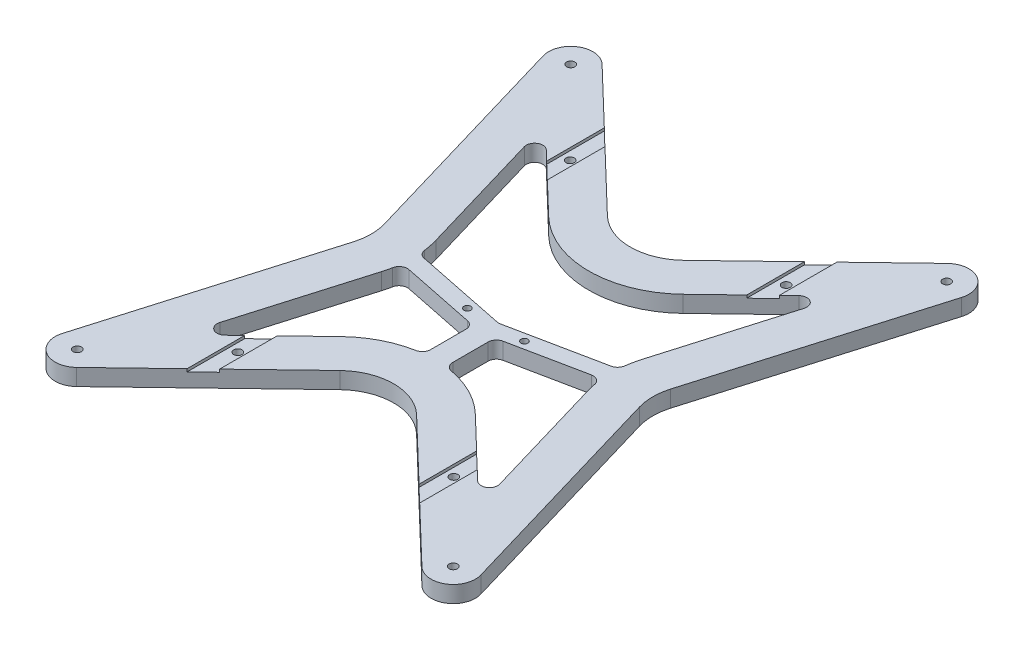
SolidWorks part; units mm, degrees
material "1060 Alloy"
ref_plane "Front Plane" through (0, 0, 0) normal (0, 0, 1) x (1, 0, 0)
ref_plane "Top Plane" through (0, 0, 0) normal (0, 1, 0) x (1, 0, 0)
ref_plane "Right Plane" through (0, 0, 0) normal (1, 0, 0) x (0, 0, -1)
sketch "Sketch1" plane through (0, 0, 0) normal (0, 1, 0) x (1, 0, 0)
  line L0 (-62.3411, 94.8657) -> (0, 35)
  line L1 (0, 35) -> (62.3411, 94.8657)
  line L2 (75.5568, 86.8368) -> (50, 0)
  line L3 (50, 0) -> (75.5568, -86.8368)
  line L4 (62.3411, -94.8657) -> (0, -35)
  line L5 (0, -35) -> (-62.3411, -94.8657)
  line L6 (-75.5568, -86.8368) -> (-50, 0)
  line L7 (-50, 0) -> (-75.5568, 86.8368)
  line L8 (-78.4889, 78.4889) -> (78.4889, -78.4889) construction
  line L9 (-42, 70) -> (-36, 70) construction
  line L10 (-42, 70) -> (-42, 50) construction
  line L11 (-42, 50) -> (-36, 50) construction
  line L12 (-36, 70) -> (-36, 50) construction
  line L13 (-42, 70) -> (-36, 50) construction
  line L14 (-42, 50) -> (-36, 70) construction
  line L15 (36, 70) -> (42, 70) construction
  line L16 (36, 70) -> (36, 50) construction
  line L17 (36, 50) -> (42, 50) construction
  line L18 (42, 70) -> (42, 50) construction
  line L19 (36, 70) -> (42, 50) construction
  line L20 (36, 50) -> (42, 70) construction
  line L21 (36, -50) -> (42, -50) construction
  line L22 (36, -50) -> (36, -70) construction
  line L23 (36, -70) -> (42, -70) construction
  line L24 (42, -50) -> (42, -70) construction
  line L25 (36, -50) -> (42, -70) construction
  line L26 (36, -70) -> (42, -50) construction
  line L27 (-42, -50) -> (-36, -50) construction
  line L28 (-42, -50) -> (-42, -70) construction
  line L29 (-42, -70) -> (-36, -70) construction
  line L30 (-36, -50) -> (-36, -70) construction
  line L31 (-42, -50) -> (-36, -70) construction
  line L32 (-42, -70) -> (-36, -50) construction
  line L33 (111, 45.9777) -> (45.9777, 111) construction
  line L34 (45.9777, 111) -> (-45.9777, 111) construction
  line L35 (-45.9777, 111) -> (-111, 45.9777) construction
  line L36 (-111, 45.9777) -> (-111, -45.9777) construction
  line L37 (-111, -45.9777) -> (-45.9777, -111) construction
  line L38 (-45.9777, -111) -> (45.9777, -111) construction
  line L39 (45.9777, -111) -> (111, -45.9777) construction
  line L40 (111, -45.9777) -> (111, 45.9777) construction
  line L41 (78.4889, 78.4889) -> (-78.4889, -78.4889) construction
  circle A0 centre (-67.8823, 89.0955) radius 1.5
  circle A1 centre (67.8823, 89.0955) radius 1.5
  circle A2 centre (-67.8823, -89.0955) radius 1.5
  circle A3 centre (67.8823, -89.0955) radius 1.5
  arc A4 (-62.3411, 94.8657) -> (-75.5568, 86.8368) centre (-67.8823, 89.0955) ccw
  arc A5 (62.3411, 94.8657) -> (75.5568, 86.8368) centre (67.8823, 89.0955) cw
  arc A6 (-75.5568, -86.8368) -> (-62.3411, -94.8657) centre (-67.8823, -89.0955) ccw
  arc A7 (75.5568, -86.8368) -> (62.3411, -94.8657) centre (67.8823, -89.0955) cw
  circle A8 centre (0, 0) radius 111 construction
  circle A9 centre (-39, 60) radius 1.5
  circle A10 centre (39, 60) radius 1.5
  circle A11 centre (39, -60) radius 1.5
  circle A12 centre (-39, -60) radius 1.5
  ellipse E0 centre (0, 0) end of major axis (50, 0) minor radius 35 construction
  dimension "D5" = 3
  dimension "D6" = 35
  dimension "D7" = 8
  dimension "D12" = 3
  dimension "D3" = 15
  dimension "D4" = 15
  dimension "D8" = 120
  dimension "D9" = 78
  dimension "D10" = 0
  dimension "D11" = 60
  dimension "D13" = 50
  dimension "D14" = 39
  dimension "D15" = 20
  dimension "D16" = 6
  dimension "D17" = 111
  dimension "D18" = 15
extrude "Boss-Extrude1" add sketch "Sketch1" along normal blind 6
fillet "Fillet1" radius 20 4 edges at (0, 3, -35) (-50, 3, 0) (0, 3, 35) (50, 3, 0)
sketch "Sketch2" plane through (0, 6, 0) normal (0, 1, 0) x (1, 0, 0)
  line L44 (-53.7292, 65.7994) -> (-37.2721, 9.8817)
  line L45 (-37.2721, -9.8817) -> (-53.7292, -65.7994)
  line L46 (-53.7292, -65.7994) -> (-24.2425, -37.4835)
  line L47 (24.2425, -37.4835) -> (53.7292, -65.7994)
  line L48 (53.7292, -65.7994) -> (37.2721, -9.8817)
  line L49 (37.2721, 9.8817) -> (53.7292, 65.7994)
  line L50 (53.7292, 65.7994) -> (24.2425, 37.4835)
  line L51 (-24.2425, 37.4835) -> (-53.7292, 65.7994)
  line L52 (-53.7292, 65.7994) -> (-37.2721, 9.8817)
  line L53 (-37.2721, -9.8817) -> (-53.7292, -65.7994)
  line L54 (-53.7292, -65.7994) -> (-24.2425, -37.4835)
  line L55 (24.2425, -37.4835) -> (53.7292, -65.7994)
  line L56 (53.7292, -65.7994) -> (37.2721, -9.8817)
  line L57 (37.2721, 9.8817) -> (53.7292, 65.7994)
  line L58 (53.7292, 65.7994) -> (24.2425, 37.4835)
  line L59 (-24.2425, 37.4835) -> (-53.7292, 65.7994)
  arc A40 (-37.2721, -9.8817) -> (-37.2721, 9.8817) centre (-70.8482, 0) ccw
  arc A41 (24.2425, -37.4835) -> (-24.2425, -37.4835) centre (0, -62.7284) ccw
  arc A42 (37.2721, 9.8817) -> (37.2721, -9.8817) centre (70.8482, 0) ccw
  arc A43 (-24.2425, 37.4835) -> (24.2425, 37.4835) centre (0, 62.7284) ccw
  arc A44 (-37.2721, -9.8817) -> (-37.2721, 9.8817) centre (-70.8482, 0) ccw
  arc A45 (24.2425, -37.4835) -> (-24.2425, -37.4835) centre (0, -62.7284) ccw
  arc A46 (37.2721, 9.8817) -> (37.2721, -9.8817) centre (70.8482, 0) ccw
  arc A47 (-24.2425, 37.4835) -> (24.2425, 37.4835) centre (0, 62.7284) ccw
  dimension "D1" = 15
extrude "Cut-Extrude1" cut sketch "Sketch2" against normal up to next
sketch "Sketch5" plane through (0, 6, 0) normal (0, 1, 0) x (1, 0, 0)
  line L0 (-38.2479, 2.9393) -> (0, -4.8715)
  line L1 (-12.94, -8.43) -> (12.94, -8.43) construction
  line L2 (-12.94, -8.43) -> (-12.94, 8.43) construction
  line L3 (-12.94, 8.43) -> (12.94, 8.43) construction
  line L4 (12.94, -8.43) -> (12.94, 8.43) construction
  line L5 (-12.94, -8.43) -> (12.94, 8.43) construction
  line L6 (-12.94, 8.43) -> (12.94, -8.43) construction
  line L8 (0, -4.8715) -> (38.2479, 2.9393)
  line L10 (38.2479, 2.9393) -> (39.4484, -2.9393)
  line L11 (39.4484, -2.9393) -> (4, -10.1785)
  line L12 (4, -10.1785) -> (4, -27.9577)
  line L13 (-4, -27.9577) -> (-4, -10.1785)
  line L14 (-4, -10.1785) -> (-39.4484, -2.9393)
  line L15 (-39.4484, -2.9393) -> (-38.2479, 2.9393)
  line L17 (38.8482, 0) -> (-38.8482, 0) construction
  circle A0 centre (-10.3, -5.83) radius 1.25
  circle A1 centre (10.3, -5.83) radius 1.25
  arc A2 (24.2425, -37.4835) -> (-24.2425, -37.4835) centre (0, -62.7284) ccw construction
  arc A3 (4, -27.9577) -> (-4, -27.9577) centre (0, -62.7284) ccw
  arc A4 (-37.2721, -9.8817) -> (-37.2721, 9.8817) centre (-70.8482, 0) ccw construction
  arc A5 (37.2721, 9.8817) -> (37.2721, -9.8817) centre (70.8482, 0) ccw construction
  circle A6 centre (38.8482, 0) radius 3 construction
  circle A7 centre (-38.8482, 0) radius 3 construction
  point P0 (0, 0)
  dimension "D3" = 2.5
  dimension "D10" = 6
  dimension "D1" = 16.86
  dimension "D2" = 25.88
  dimension "D4" = 20.6
  dimension "D5" = 2.64
  dimension "D6" = 2.6
  dimension "D7" = 6
  dimension "D8" = 3
  dimension "D9" = 8
extrude "Boss-Extrude2" add sketch "Sketch5" against normal up to surface (6 mm away) up to face at (0, 0, 0)
fillet "Fillet2" radius 3 13 edges at (53.7292, 3, 65.7994) (-53.7292, 3, 65.7994) (53.7292, 3, -65.7994) (-53.7292, 3, -65.7994) (0, 3, 4.8715) (4, 3, 10.1785) (4, 3, 27.9577) (-4, 3, 27.9577) (-4, 3, 10.1785) (35.9352, 3, -2.467) (-35.9352, 3, -2.467) (36.0376, 3, 3.6359) (-36.0376, 3, 3.6359)
sketch "Sketch6" plane through (0, 6, 0) normal (0, 1, 0) x (1, 0, 0)
  line L0 (-13.8528, 48.3028) -> (-62.3411, 94.8657) construction
  line L1 (-42, -48) -> (-36, -48)
  line L2 (-42, -48) -> (-42, -75.3323)
  line L3 (-42, -75.3323) -> (-36, -75.3323)
  line L4 (-36, -48) -> (-36, -75.3323)
  line L5 (36, -48) -> (42, -48)
  line L6 (36, -48) -> (36, -75.3323)
  line L7 (36, -75.3323) -> (42, -75.3323)
  line L8 (42, -48) -> (42, -75.3323)
  line L9 (36, 48) -> (42, 48)
  line L10 (36, 48) -> (36, 75.3323)
  line L11 (36, 75.3323) -> (42, 75.3323)
  line L12 (42, 48) -> (42, 75.3323)
  line L13 (-42, 48) -> (-36, 48)
  line L14 (-42, 48) -> (-42, 75.3323)
  line L15 (-42, 75.3323) -> (-36, 75.3323)
  line L16 (-36, 48) -> (-36, 75.3323)
  line L17 (62.3411, 94.8657) -> (13.8528, 48.3028) construction
  line L18 (13.8528, -48.3028) -> (62.3411, -94.8657) construction
  line L19 (-62.3411, -94.8657) -> (-13.8528, -48.3028) construction
  circle A0 centre (-39, -60) radius 1.5 construction
  circle A1 centre (39, -60) radius 1.5 construction
  circle A2 centre (-39, 60) radius 1.5 construction
  dimension "D2" = 3
  dimension "D3" = 3
  dimension "D5" = 12
  dimension "D1" = 6
  dimension "D4" = 12
extrude "Cut-Extrude2" cut sketch "Sketch6" against normal blind 1
equation "\"D14@Sketch1\"=\"D9@Sketch1\"/2"
